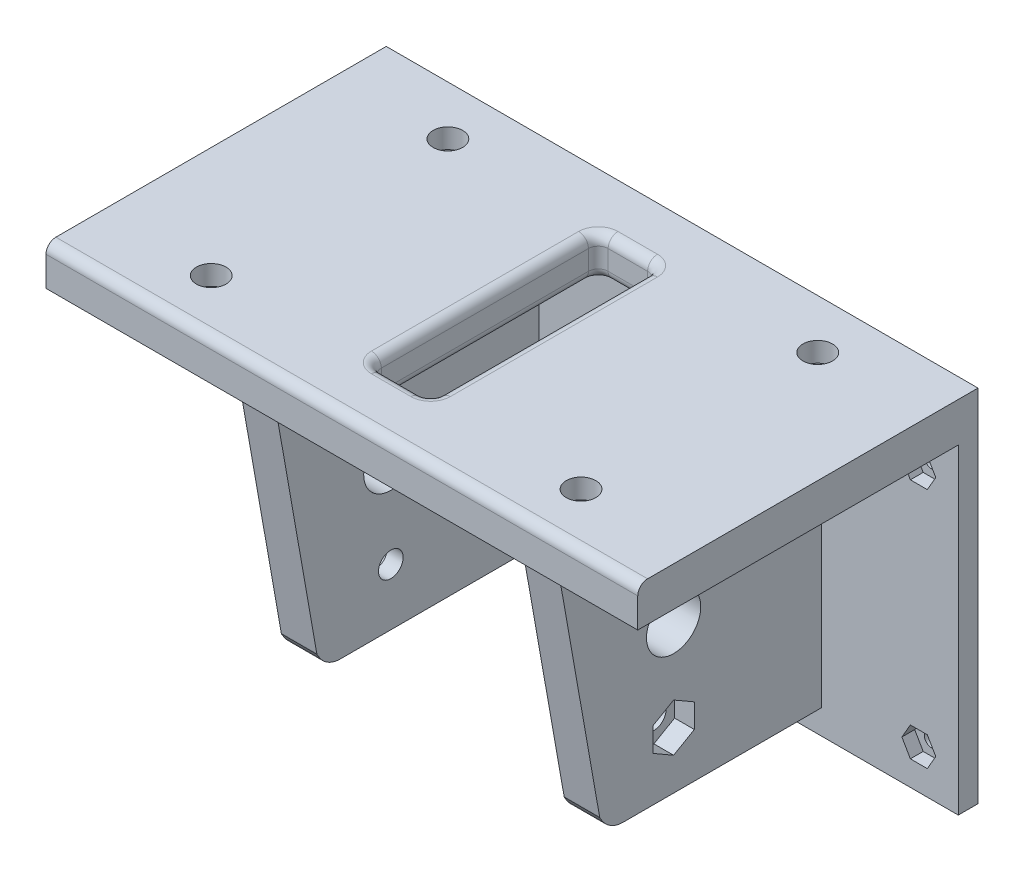
SolidWorks part; units mm, degrees
ref_plane "Front Plane" through (0, 0, 0) normal (0, 0, 1) x (1, 0, 0)
ref_plane "Top Plane" through (0, 0, 0) normal (0, 1, 0) x (1, 0, 0)
ref_plane "Right Plane" through (0, 0, 0) normal (1, 0, 0) x (0, 0, -1)
sketch "Sketch1" plane through (0, 0, 0) normal (0, 1, 0) x (1, 0, 0)
  line L0 (0, 18.2197) -> (0, -18.3609) construction
  line L1 (-19.3496, 0) -> (20.197, 0) construction
  line L2 (-37.5, 0) -> (-37.5, -10) construction
  line L3 (60, 35) -> (-60, 35)
  line L4 (-60, 35) -> (-60, -35)
  line L5 (60, -35) -> (-60, -35)
  line L6 (60, 35) -> (60, -35)
  line L7 (6, 23) -> (-6, 23)
  line L8 (-6, 23) -> (-6, -23)
  line L9 (6, -23) -> (-6, -23)
  line L10 (6, 23) -> (6, -23)
  circle A0 centre (-37.5, 0) radius 10 construction
  circle A6 centre (-37.5, 24) radius 3
  circle A7 centre (-37.5, 24) radius 3.4 construction
  circle A8 centre (-37.5, -24) radius 3
  circle A9 centre (-37.5, -24) radius 3.4 construction
  circle A10 centre (37.5, 24) radius 3
  circle A11 centre (37.5, 24) radius 3.4 construction
  circle A12 centre (37.5, 0) radius 10 construction
  circle A13 centre (37.5, -24) radius 3.4 construction
  circle A14 centre (37.5, -24) radius 3
  point P18 (-60, 0)
  point P20 (0, 35)
  point P21 (0, -35)
  point P33 (-6, 0)
  point P35 (0, -23)
  point P36 (0, 23)
  dimension "D1" = 20
  dimension "D3" = 6.8
  dimension "D4" = 48
  dimension "D5" = 75
  dimension "D2" = 6
  dimension "D6" = 120
  dimension "D7" = 70
  dimension "D8" = 12
  dimension "D9" = 46
extrude "Boss-Extrude1" add sketch "Sketch1" along normal blind 8
fillet "Fillet1" radius 2 4 edges at (6, 4, 23) (-6, 4, 23) (6, 4, -23) (-6, 4, -23)
sketch "Sketch2" plane through (0, 0, 0) normal (0, -1, 0) x (1, 0, 0)
  line L0 (-60, -35) -> (-60, -30)
  line L1 (-60, -35) -> (-60, 35) construction
  line L2 (-60, -30) -> (60, -30)
  line L3 (60, 35) -> (60, -35) construction
  line L4 (60, -30) -> (60, -35)
  line L5 (60, -35) -> (-60, -35)
  dimension "D1" = 5
extrude "Boss-Extrude2" add sketch "Sketch2" along normal blind 65
sketch "Sketch3" plane through (0, 0, -30) normal (0, 0, 1) x (1, 0, 0)
  line L0 (0, 0) -> (0, -65) construction
  line L1 (60, 0) -> (-60, 0) construction
  line L2 (60, -65) -> (-60, -65) construction
  line L3 (0, -32.5) -> (-60, -32.5) construction
  line L4 (-60, -65) -> (-60, 0) construction
  line L5 (0, -32.5) -> (60, -32.5) construction
  line L6 (60, -65) -> (60, 0) construction
  line L8 (30, 0) -> (30, -65) construction
  line L9 (-25.075, 0) -> (-32.275, 0)
  line L10 (-32.275, 0) -> (-32.275, -60)
  line L11 (-32.275, -60) -> (-25.075, -60)
  line L12 (-25.075, 0) -> (-25.075, -60)
  line L13 (25.075, 0) -> (25.075, -60)
  line L14 (32.275, -60) -> (25.075, -60)
  line L15 (32.275, 0) -> (32.275, -60)
  line L16 (25.075, 0) -> (32.275, 0)
  point P18 (30, -32.5)
  dimension "D1" = 7.2
  dimension "D2" = 50.15
  dimension "D3" = 60
extrude "Boss-Extrude3" add sketch "Sketch3" along normal blind 45
sketch "Sketch4" plane through (-32.275, 0, 0) normal (-1, 0, 0) x (0, 0, 1)
  line L0 (0, 0) -> (0, -60) construction
  line L1 (15, -60) -> (-30, -60) construction
  line L2 (-30, -30) -> (15, -30) construction
  line L3 (-30, 0) -> (-30, -60) construction
  line L4 (15, 0) -> (15, -60) construction
  circle A0 centre (0, -30) radius 5.5
  circle A1 centre (0, -30) radius 18.5 construction
  circle A2 centre (0, -11.5) radius 2.5
  circle A3 centre (0, -48.5) radius 2.5
  dimension "D1" = 11
  dimension "D2" = 37
  dimension "5" = 5
extrude "Cut-Extrude1" cut sketch "Sketch4" against normal through all both and the other way through all
sketch "Sketch5" plane through (-32.275, 0, 0) normal (-1, 0, 0) x (0, 0, 1)
  line L0 (-30, 0) -> (-30, -60) construction
  line L1 (4.2, -9.0751) -> (0, -6.6503)
  line L2 (0, -6.6503) -> (-4.2, -9.0751)
  line L3 (-4.2, -9.0751) -> (-4.2, -13.9249)
  line L4 (-4.2, -13.9249) -> (0, -16.3497)
  line L5 (0, -16.3497) -> (4.2, -13.9249)
  line L6 (4.2, -13.9249) -> (4.2, -9.0751)
  line L7 (4.2, -46.0751) -> (0, -43.6503)
  line L8 (0, -43.6503) -> (-4.2, -46.0751)
  line L9 (-4.2, -46.0751) -> (-4.2, -50.9249)
  line L10 (-4.2, -50.9249) -> (0, -53.3497)
  line L11 (0, -53.3497) -> (4.2, -50.9249)
  line L12 (4.2, -50.9249) -> (4.2, -46.0751)
  line L13 (-30, -65) -> (-30, 0) construction
  circle A0 centre (0, -11.5) radius 4.2 construction
  circle A1 centre (0, -48.5) radius 4.2 construction
  point P10 (2.1, -52.1373)
  dimension "D1" = 8.4
  dimension "D2" = 8.4
extrude "Cut-Extrude2" cut sketch "Sketch5" against normal blind 4
sketch "Sketch6" plane through (32.275, 0, 0) normal (1, 0, 0) x (0, 0, -1)
  line L0 (30, -65) -> (30, 0) construction
  line L1 (4.2, -13.9249) -> (4.2, -9.0751)
  line L2 (4.2, -9.0751) -> (0, -6.6503)
  line L3 (0, -6.6503) -> (-4.2, -9.0751)
  line L4 (-4.2, -9.0751) -> (-4.2, -13.9249)
  line L5 (-4.2, -13.9249) -> (0, -16.3497)
  line L6 (0, -16.3497) -> (4.2, -13.9249)
  line L7 (-4.2, -46.0751) -> (-4.2, -50.9249)
  line L8 (-4.2, -50.9249) -> (0, -53.3497)
  line L9 (0, -53.3497) -> (4.2, -50.9249)
  line L10 (4.2, -50.9249) -> (4.2, -46.0751)
  line L11 (4.2, -46.0751) -> (0, -43.6503)
  line L12 (0, -43.6503) -> (-4.2, -46.0751)
  circle A0 centre (0, -11.5) radius 4.2 construction
  circle A1 centre (0, -48.5) radius 4.2 construction
  dimension "D1" = 8.4
  dimension "D2" = 8.4
extrude "Cut-Extrude3" cut sketch "Sketch6" against normal blind 4
sketch "Sketch7" plane through (0, 0, 0) normal (0, -1, 0) x (1, 0, 0)
  line L0 (32.275, 15) -> (32.275, -30) construction
  line L1 (42.7, -20.9978) -> (37.5, -17.9956)
  line L2 (37.5, -17.9956) -> (32.3, -20.9978)
  line L3 (32.3, -20.9978) -> (32.3, -27.0022)
  line L4 (32.3, -27.0022) -> (37.5, -30.0044)
  line L5 (37.5, -30.0044) -> (42.7, -27.0022)
  line L6 (42.7, -27.0022) -> (42.7, -20.9978)
  line L7 (42.7, 27.0022) -> (37.5, 30.0044)
  line L8 (37.5, 30.0044) -> (32.3, 27.0022)
  line L9 (32.3, 27.0022) -> (32.3, 20.9978)
  line L10 (32.3, 20.9978) -> (37.5, 17.9956)
  line L11 (37.5, 17.9956) -> (42.7, 20.9978)
  line L12 (42.7, 20.9978) -> (42.7, 27.0022)
  line L13 (0, 0) -> (0, 40) construction
  line L14 (-42.7, -27.0022) -> (-42.7, -20.9978)
  line L15 (-37.5, -30.0044) -> (-42.7, -27.0022)
  line L16 (-32.3, -27.0022) -> (-37.5, -30.0044)
  line L17 (-32.3, -20.9978) -> (-32.3, -27.0022)
  line L18 (-37.5, -17.9956) -> (-32.3, -20.9978)
  line L19 (-42.7, -20.9978) -> (-37.5, -17.9956)
  line L20 (-42.7, 20.9978) -> (-42.7, 27.0022)
  line L21 (-37.5, 17.9956) -> (-42.7, 20.9978)
  line L22 (-32.3, 20.9978) -> (-37.5, 17.9956)
  line L23 (-32.3, 27.0022) -> (-32.3, 20.9978)
  line L24 (-37.5, 30.0044) -> (-32.3, 27.0022)
  line L25 (-42.7, 27.0022) -> (-37.5, 30.0044)
  circle A0 centre (37.5, -24) radius 5.2 construction
  circle A1 centre (37.5, 24) radius 5.2 construction
  circle A3 centre (-37.5, -24) radius 5.2 construction
  circle A4 centre (-37.5, 24) radius 5.2 construction
  dimension "D1" = 10.4
  dimension "D2" = 10.4
extrude "Cut-Extrude4" cut sketch "Sketch7" against normal blind 4
sketch "Sketch8" plane through (32.275, 0, 0) normal (1, 0, 0) x (0, 0, -1)
  circle A0 centre (0, -30) radius 9.515 construction
  circle A1 centre (0, -20.485) radius 1.5
  circle A2 centre (0, -39.515) radius 1.5
  dimension "D1" = 19.03
  dimension "D2" = 3
extrude "Cut-Extrude5" [suppressed] cut sketch "Sketch8" against normal up to surface (7.2 mm away) up to face at (25.075, -48.5, -2.5)
sketch "Sketch9" [suppressed] plane through (25.075, 0, 0) normal (-1, 0, 0) x (0, 0, 1)
  line L1 (1.7321, -40.015) -> (3.4641, -37.015)
  line L2 (3.4641, -37.015) -> (1.7321, -34.015)
  line L3 (1.7321, -34.015) -> (-1.7321, -34.015)
  line L4 (-1.7321, -34.015) -> (-3.4641, -37.015)
  line L5 (-3.4641, -37.015) -> (-1.7321, -40.015)
  line L6 (-1.7321, -40.015) -> (1.7321, -40.015)
  line L7 (1.7321, -20.985) -> (3.4641, -17.985)
  line L8 (3.4641, -17.985) -> (1.7321, -14.985)
  line L9 (1.7321, -14.985) -> (-1.7321, -14.985)
  line L10 (-1.7321, -14.985) -> (-3.4641, -17.985)
  line L11 (-3.4641, -17.985) -> (-1.7321, -20.985)
  line L12 (-1.7321, -20.985) -> (1.7321, -20.985)
  line L13 (15, -55) -> (-30, -55) construction
  circle A0 centre (0, -37.015) radius 3 construction
  circle A1 centre (0, -17.985) radius 3 construction
  dimension "D1" = 6
  dimension "D2" = 6
extrude "Cut-Extrude6" [suppressed] cut sketch "Sketch9" against normal blind 3.5
chamfer "Chamfer1" distance 10 angle 80 2 edges at (-28.675, 0, 15) (28.675, 0, 15) first distance on face at (37.5, 0, 24)
fillet "Fillet3" radius 2 17 edges at (5.4142, 0, 22.4142) (0, 0, 23) (-5.4142, 0, 22.4142) (-6, 0, 0) (-5.4142, 0, -22.4142) (0, 0, -23) (5.4142, 0, -22.4142) (5.4142, 8, 22.4142) (0, 8, 23) (-5.4142, 8, 22.4142) (-6, 8, 0) (-5.4142, 8, -22.4142) (0, 8, -23) (5.4142, 8, -22.4142) (6, 0, 0) (6, 8, 0) (0, 8, 35)
chamfer "Chamfer2" distance 2 angle 58 2 edges at (28.675, -60, 15) (-28.675, -60, 15) first distance on face at (28.675, -60, -7.5) first distance on face at (-28.675, -60, -7.5)
fillet "Fillet4" radius 5 2 edges at (-28.675, -60, 13) (28.675, -60, 13)
chamfer "Chamfer3" distance 1 angle 45 4 edges at (0, 8, -35) (-60, -28.5, -35) (0, -65, -35) (60, -28.5, -35)
sketch "Sketch11" plane through (0, 0, -30) normal (0, 0, 1) x (1, 0, 0)
  line L0 (-60, 0) -> (60, 0) construction
  line L1 (-60, -65) -> (-60, 0) construction
  line L2 (60, -65) -> (-60, -65) construction
  line L3 (60, -65) -> (60, 0) construction
  circle A0 centre (-52, -8) radius 1.5
  circle A1 centre (-52, -57) radius 1.5
  circle A2 centre (52, -8) radius 1.5
  circle A3 centre (52, -57) radius 1.5
  dimension "D3" = 3
  dimension "D1" = 8
  dimension "D2" = 8
  dimension "D4" = 8
  dimension "D5" = 8
  dimension "D6" = 8
  dimension "D7" = 8
  dimension "D8" = 8
  dimension "D9" = 8
extrude "Cut-Extrude7" cut sketch "Sketch11" against normal blind 10
sketch "Sketch12" plane through (0, 0, -30) normal (0, 0, 1) x (1, 0, 0)
  line L1 (-48.5648, -8) -> (-50.2824, -5.025)
  line L2 (-50.2824, -5.025) -> (-53.7176, -5.025)
  line L3 (-53.7176, -5.025) -> (-55.4352, -8)
  line L4 (-55.4352, -8) -> (-53.7176, -10.975)
  line L5 (-53.7176, -10.975) -> (-50.2824, -10.975)
  line L6 (-50.2824, -10.975) -> (-48.5648, -8)
  line L7 (-48.5648, -57) -> (-50.2824, -54.025)
  line L8 (-50.2824, -54.025) -> (-53.7176, -54.025)
  line L9 (-53.7176, -54.025) -> (-55.4352, -57)
  line L10 (-55.4352, -57) -> (-53.7176, -59.975)
  line L11 (-53.7176, -59.975) -> (-50.2824, -59.975)
  line L12 (-50.2824, -59.975) -> (-48.5648, -57)
  line L13 (55.4352, -57) -> (53.7176, -54.025)
  line L14 (53.7176, -54.025) -> (50.2824, -54.025)
  line L15 (50.2824, -54.025) -> (48.5648, -57)
  line L16 (48.5648, -57) -> (50.2824, -59.975)
  line L17 (50.2824, -59.975) -> (53.7176, -59.975)
  line L18 (53.7176, -59.975) -> (55.4352, -57)
  line L19 (55.4352, -8) -> (53.7176, -5.025)
  line L20 (53.7176, -5.025) -> (50.2824, -5.025)
  line L21 (50.2824, -5.025) -> (48.5648, -8)
  line L22 (48.5648, -8) -> (50.2824, -10.975)
  line L23 (50.2824, -10.975) -> (53.7176, -10.975)
  line L24 (53.7176, -10.975) -> (55.4352, -8)
  circle A0 centre (-52, -8) radius 2.975 construction
  circle A1 centre (-52, -57) radius 2.975 construction
  circle A2 centre (52, -57) radius 2.975 construction
  circle A3 centre (52, -8) radius 2.975 construction
  dimension "D1" = 5.95
  dimension "D2" = 5.95
  dimension "D3" = 5.95
  dimension "D4" = 5.95
extrude "Cut-Extrude8" cut sketch "Sketch12" against normal blind 2.6
